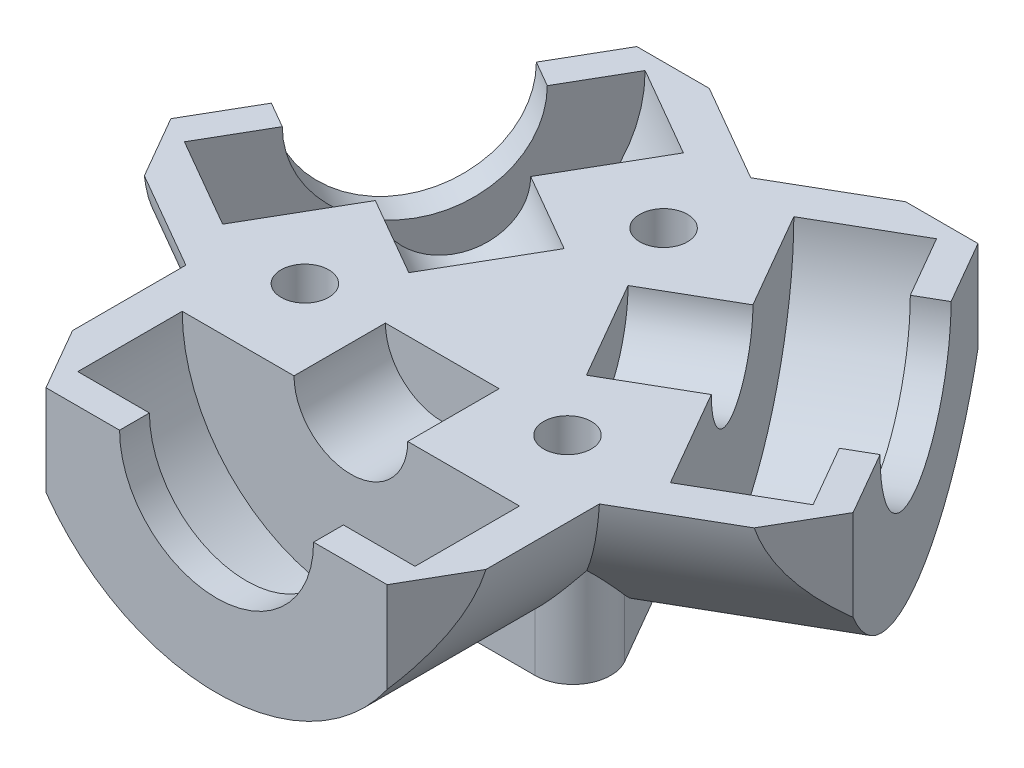
SolidWorks part; units mm, degrees
ref_plane "Front Plane" through (0, 0, 0) normal (0, 0, 1) x (1, 0, 0)
ref_plane "Top Plane" through (0, 0, 0) normal (0, 1, 0) x (1, 0, 0)
ref_plane "Right Plane" through (0, 0, 0) normal (1, 0, 0) x (0, 0, -1)
sketch "Sketch1" plane through (0, 0, 0) normal (0, 1, 0) x (1, 0, 0)
  line L1 (11.43, -19.7973) -> (22.86, 0)
  line L2 (22.86, 0) -> (11.43, 19.7973)
  line L3 (11.43, 19.7973) -> (-11.43, 19.7973)
  line L4 (-11.43, 19.7973) -> (-22.86, 0)
  line L5 (-22.86, 0) -> (-11.43, -19.7973)
  line L6 (-11.43, -19.7973) -> (11.43, -19.7973)
  circle A0 centre (0, 0) radius 19.7973 construction
  dimension "D1" = 22.86
extrude "Boss-Extrude1" add sketch "Sketch1" along normal blind 12.7 contours L4 L5 L6 L1 L2 L3
sketch "Sketch5" plane through (0, 12.7, 0) normal (0, 1, 0) x (1, 0, 0)
  line L14 (0, -19.7973) -> (0, -4.6723)
  line L15 (-11.43, -19.7973) -> (11.43, -19.7973) construction
  line L16 (0, -4.6723) -> (-3.81, -4.6723)
  line L17 (-3.81, -4.6723) -> (-3.81, -10.7973)
  line L18 (-3.81, -10.7973) -> (-11.3, -10.7973)
  line L19 (-11.3, -10.7973) -> (-11.3, -17.7973)
  line L20 (-11.3, -17.7973) -> (-6.5, -17.7973)
  line L21 (-6.5, -17.7973) -> (-6.5, -19.7973)
  line L22 (-6.5, -19.7973) -> (0, -19.7973)
  dimension "D1" = 6.5
  dimension "D2" = 11.3
  dimension "D3" = 2
  dimension "D4" = 7
  dimension "D5" = 6.125
  dimension "D6" = 3.81
revolve "Cut-Revolve1" cut sketch "Sketch5" angle 360 about L14
sketch "Sketch7" plane through (0, 12.7, 0) normal (0, 1, 0) x (1, 0, 0)
  circle A0 centre (0, 10.16) radius 1.6
  circle A1 centre (8.7988, -5.08) radius 1.6
  circle A2 centre (-8.7988, -5.08) radius 1.6
  circle A3 centre (0, 0) radius 10.16 construction
  point P11 (0, 0)
  dimension "D1" = 3.2
  dimension "D2" = 20.32
  dimension "D3" = 3
extrude "Cut-Extrude2" cut sketch "Sketch7" against normal up to surface (12.7 mm away) up to face at (0, 0, 0)
ref_axis "Axis1" through (0, -0.635, 0) along (0, 1, 0)
pattern_circular "CirPattern1" count 3 over 360 about axis through (0, -0.635, 0) along (0, 1, 0) of "Cut-Revolve1"
sketch "Sketch8" plane through (0, 0, 19.7973) normal (0, 0, 1) x (1, 0, 0)
  line L0 (-3.81, 12.7) -> (3.81, 12.7) construction
  line L1 (-13.8564, 12.7) -> (-18.6629, 12.7)
  line L2 (-22.86, 12.7) -> (-11.43, 12.7) construction
  line L3 (-18.6629, 12.7) -> (-18.6629, 0)
  line L4 (-22.86, 0) -> (-11.43, 0) construction
  line L5 (-18.6629, 0) -> (18.6629, 0)
  line L6 (11.43, 0) -> (22.86, 0) construction
  line L7 (18.6629, 0) -> (18.6629, 12.7)
  line L8 (11.43, 12.7) -> (22.86, 12.7) construction
  line L9 (18.6629, 12.7) -> (13.8564, 12.7)
  arc A0 (-13.8564, 12.7) -> (13.8564, 12.7) centre (0, 14.7) ccw
  dimension "D1" = 14
  dimension "D2" = 2
extrude "Cut-Extrude3" cut sketch "Sketch8" against normal blind 11.684
pattern_circular "CirPattern2" count 3 over 360 about axis through (0, -0.635, 0) along (0, 1, 0) of "Cut-Extrude3"
sketch "Sketch10" plane through (0, 0, 0) normal (0, -1, 0) x (1, 0, 0)
  line L3 (14.0527, 8.1133) -> (-14.0527, 8.1133)
  line L4 (-14.0527, 8.1133) -> (0, -16.2267)
  line L5 (0, -16.2267) -> (14.0527, 8.1133)
  line L6 (14.0527, 8.1133) -> (-14.0527, 8.1133)
  line L7 (-14.0527, 8.1133) -> (0, -16.2267)
  line L8 (0, -16.2267) -> (14.0527, 8.1133)
  dimension "D1" = 0
extrude "Cut-Extrude5" cut sketch "Sketch10" against normal blind 0.7
fillet "Fillet2" radius 2.54 3 edges at (14.0527, 6.7, 8.1133) (0, 6.7, -16.2267) (-14.0527, 6.7, 8.1133)
